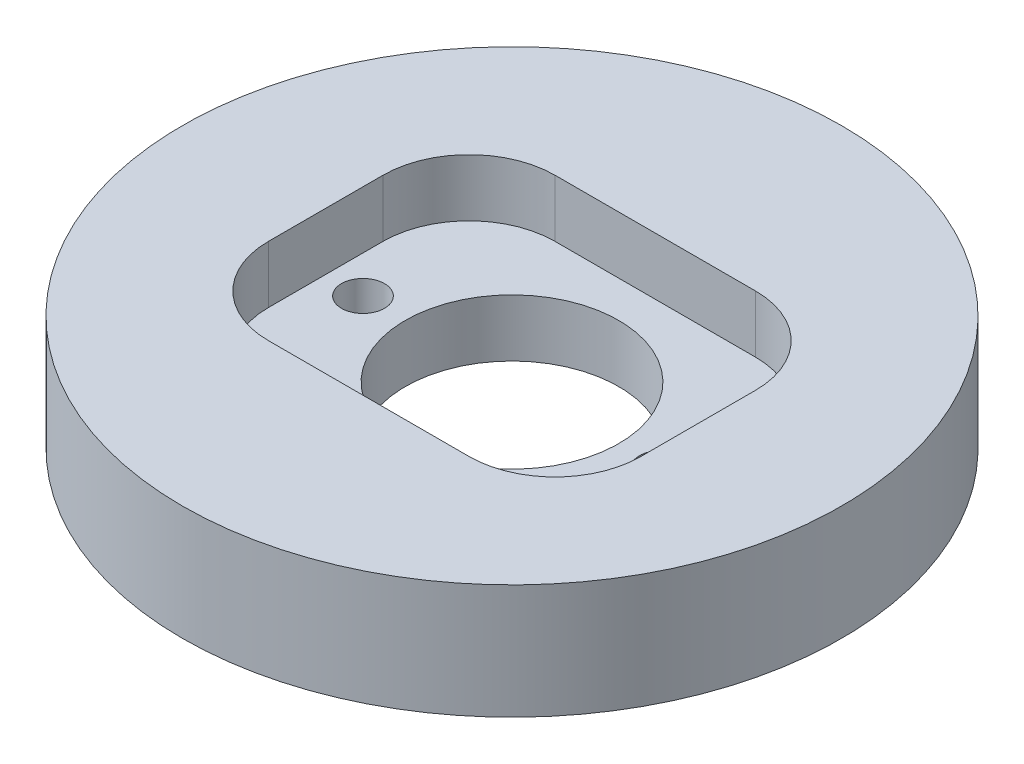
SolidWorks part; units mm, degrees
ref_plane "Front Plane" through (0, 0, 0) normal (0, 0, 1) x (1, 0, 0)
ref_plane "Top Plane" through (0, 0, 0) normal (0, 1, 0) x (1, 0, 0)
ref_plane "Right Plane" through (0, 0, 0) normal (1, 0, 0) x (0, 0, -1)
sketch "Sketch2" plane through (0, 0, 0) normal (0, 1, 0) x (1, 0, 0)
  line L0 (0, 11.5) -> (0, -22.3339) construction
  line L1 (11.5, 0) -> (-25.2541, 0) construction
  circle A0 centre (0, 0) radius 11.5
  dimension "D1" = 23
extrude "Boss-Extrude1" add sketch "Sketch2" along normal blind 4
sketch "Sketch3" plane through (0, 4, 0) normal (0, 1, 0) x (1, 0, 0)
  line L1 (-6.5, 5) -> (6.5, 5)
  line L2 (-6.5, 5) -> (-6.5, -5)
  line L3 (-6.5, -5) -> (6.5, -5)
  line L4 (6.5, 5) -> (6.5, -5)
  line L5 (-6.5, 5) -> (6.5, -5) construction
  line L6 (-6.5, -5) -> (6.5, 5) construction
  point P0 (0, 0)
  dimension "D1" = 13
  dimension "D2" = 10
extrude "Cut-Extrude1" cut sketch "Sketch3" against normal blind 2
fillet "Fillet1" radius 3 4 edges at (-6.5, 3, 5) (6.5, 3, 5) (-6.5, 3, -5) (6.5, 3, -5)
sketch "Sketch4" plane through (0, 2, 0) normal (0, 1, 0) x (1, 0, 0)
  line L1 (3.5, 5) -> (-3.5, 5) construction
  line L2 (0, 0) -> (0, -18.2909) construction
  circle A0 centre (0, 0) radius 3.725
  circle A2 centre (-5.2, 0) radius 0.75
  circle A3 centre (5.2, 0) radius 0.75
  dimension "D1" = 7.45
  dimension "D2" = 5.2
  dimension "D3" = 5
extrude "Cut-Extrude2" cut sketch "Sketch4" against normal through all
